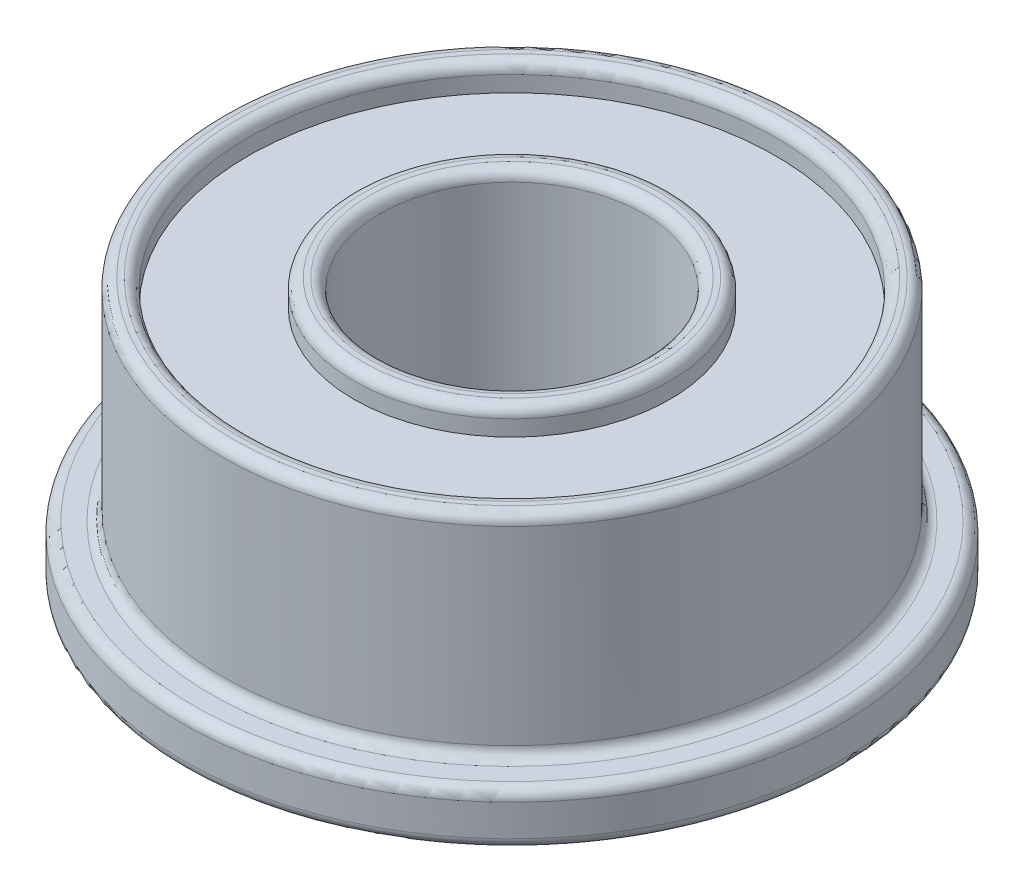
SolidWorks part; units mm, degrees
ref_plane "正面" through (0, 0, 0) normal (0, 0, 1) x (1, 0, 0)
ref_plane "平面" through (0, 0, 0) normal (0, 1, 0) x (1, 0, 0)
ref_plane "右側面" through (0, 0, 0) normal (1, 0, 0) x (0, 0, -1)
sketch "ｽｹｯﾁ1" plane through (0, 0, 0) normal (0, 1, 0) x (1, 0, 0)
  circle A0 centre (0, 0) radius 2.5
  circle A1 centre (0, 0) radius 5.5
  dimension "D1" = 5
  dimension "D2" = 11
extrude "ﾎﾞｽ - 押し出し1" add sketch "ｽｹｯﾁ1" along normal mid plane 5
sketch "ｽｹｯﾁ2" plane through (0, -2.5, 0) normal (0, -1, 0) x (1, 0, 0)
  circle A1 centre (0, 0) radius 5.5
  circle A2 centre (0, 0) radius 5.5
  dimension "D1" = 0
extrude "押し出し-薄板1" add sketch "ｽｹｯﾁ2" against normal blind 1 thin thin type one direction wall 0.75
sketch "ｽｹｯﾁ3" plane through (0, 2.5, 0) normal (0, 1, 0) x (1, 0, 0)
  circle A1 centre (0, 0) radius 2.5 construction
  circle A2 centre (0, 0) radius 5
  circle A3 centre (0, 0) radius 5
  circle A4 centre (0, 0) radius 5.5
  circle A5 centre (0, 0) radius 5.5
  circle A6 centre (0, 0) radius 2.5
  circle A7 centre (0, 0) radius 3
  dimension "D1" = 0.5
  dimension "D2" = 0
  dimension "D3" = 0.5
extrude "ｶｯﾄ - 押し出し1" cut sketch "ｽｹｯﾁ3" against normal mid plane 1 contours A3 A7 region at (-4.8586, 2.5, 0)
mirror "ﾐﾗｰ1" about plane through (0, 0, 0) normal (0, 1, 0) of "ｶｯﾄ - 押し出し1"
fillet "ﾌｨﾚｯﾄ1" radius 0.2 9 edges at (0, -2.5, 5) (0, -2.5, 3) (0, 2.5, 5) (0, 2.5, 3) (6.25, -2.5, 0) (0, -2.5, 2.5) (0, 2.5, 2.5) (0, -1.5, -5.5) (0, 2.5, 5.5)
fillet "ﾌｨﾚｯﾄ2" radius 0.2 1 edges at (6.25, -1.5, 0)
